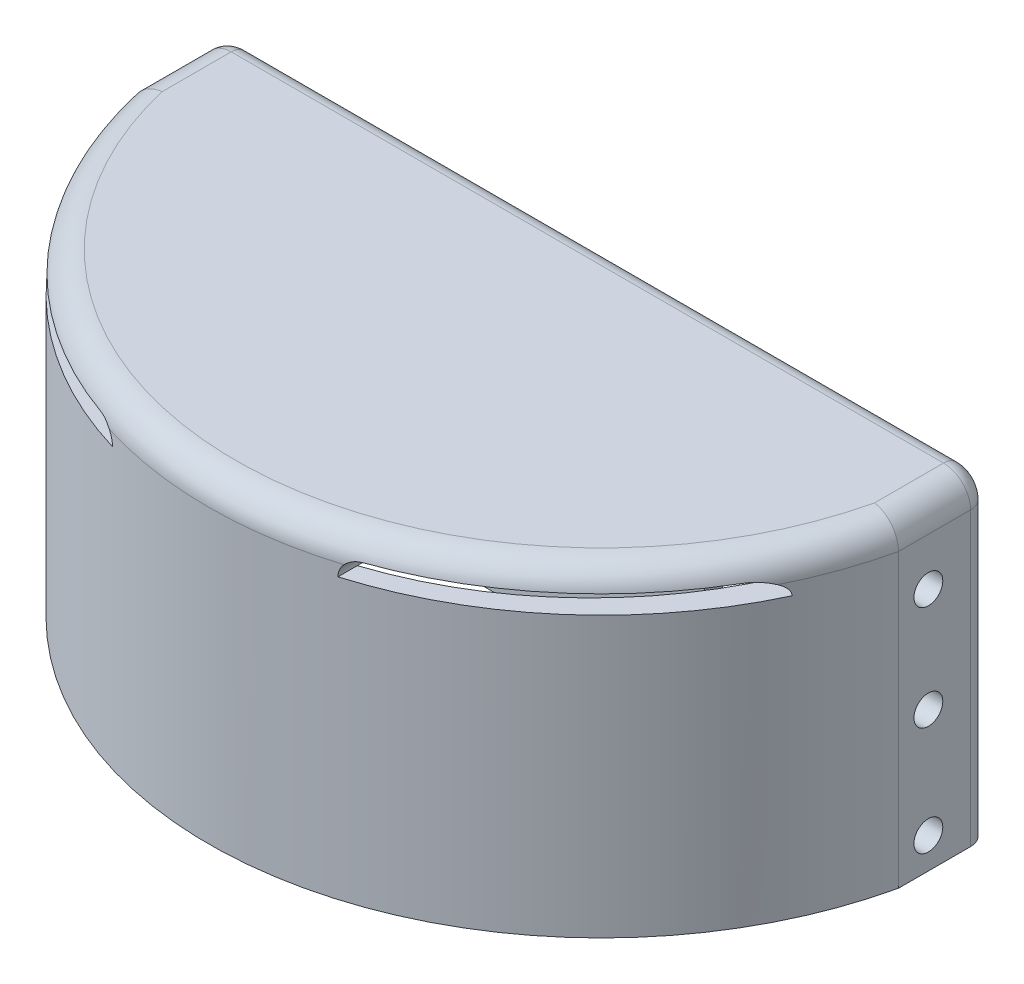
SolidWorks part; units mm, degrees
ref_plane "Ön Düzlem" through (0, 0, 0) normal (0, 0, 1) x (1, 0, 0)
ref_plane "Üst Düzlem" through (0, 0, 0) normal (0, 1, 0) x (1, 0, 0)
ref_plane "Sağ Düzlem" through (0, 0, 0) normal (1, 0, 0) x (0, 0, -1)
sketch "Çizim1" plane through (0, 0, 0) normal (0, 0, 1) x (1, 0, 0)
  line L1 (-11.5, 17.5) -> (11.5, 17.5)
  line L2 (-13.5, 15.5) -> (-13.5, -15.5)
  line L3 (-11.5, -17.5) -> (11.5, -17.5)
  line L4 (13.5, 15.5) -> (13.5, -15.5)
  circle A0 centre (-10, 14) radius 2.5
  circle A1 centre (-10, -14) radius 2.5
  circle A2 centre (10, 14) radius 2.5
  circle A3 centre (10, -14) radius 2.5
  arc A4 (11.5, -17.5) -> (13.5, -15.5) centre (11.5, -15.5) ccw
  arc A5 (-13.5, -15.5) -> (-11.5, -17.5) centre (-11.5, -15.5) ccw
  arc A6 (-11.5, 17.5) -> (-13.5, 15.5) centre (-11.5, 15.5) ccw
  arc A7 (11.5, 17.5) -> (13.5, 15.5) centre (11.5, 15.5) cw
  point P0 (0, 0)
  point P16 (13.5, -17.5)
  point P21 (-13.5, 17.5)
  point P24 (13.5, 17.5)
  dimension "D3" = 5
  dimension "D4" = 5
  dimension "D5" = 5
  dimension "D6" = 5
  dimension "D7" = 3.5
  dimension "D8" = 3.5
  dimension "D9" = 3.5
  dimension "D10" = 3.5
  dimension "D11" = 3.5
  dimension "D12" = 3.5
  dimension "D13" = 3.5
  dimension "D14" = 3.5
  dimension "D15" = 2
  dimension "D1" = 27
  dimension "D2" = 35
extrude "Yükseklik-Ekstrüzyon1" add sketch "Çizim1" along normal blind 2
sketch "Çizim2" plane through (0, 0, 0) normal (0, 0, -1) x (-1, 0, 0)
  line L0 (13.5, 15.5) -> (38.5, 15.5)
  line L1 (38.5, 15.5) -> (38.5, -15.5)
  line L2 (38.5, -15.5) -> (13.5, -15.5)
  line L3 (13.5, -15.5) -> (13.5, 15.5)
  dimension "D1" = 25
extrude "Yükseklik-Ekstrüzyon2" add sketch "Çizim2" against normal blind 2
sketch "Çizim3" plane through (0, 0, 0) normal (0, 0, -1) x (-1, 0, 0)
  line L0 (26, 15.5) -> (26, 12.3298)
  line L1 (38.5, 15.5) -> (13.5, 15.5) construction
  line L2 (26, 12.3298) -> (26.8882, 12.3298)
  line L3 (26.8882, 12.3298) -> (26.8882, 15.5)
  line L4 (26.8882, 15.5) -> (26, 15.5)
extrude "Kes-Ekstrüzyon1" cut sketch "Çizim3" against normal blind 2
mirror "Aynalama4" about plane through (-26, 15.5, 2) normal (1, 0, 0) of "Yükseklik-Ekstrüzyon1"
sketch "Çizim6" plane through (0, 0, 0) normal (0, 0, -1) x (-1, 0, 0)
  line L0 (-13.5, -15.5) -> (-13.5, 15.5) construction
  line L1 (-13.5, 15.5) -> (-16.5, 15.5)
  line L2 (-13.5, 15.5) -> (-13.5, -15.5)
  line L3 (-13.5, -15.5) -> (-16.5, -15.5)
  line L4 (-16.5, 15.5) -> (-16.5, -15.5)
  line L6 (65.5, 15.5) -> (68.5, 15.5)
  line L7 (65.5, 15.5) -> (65.5, -15.5)
  line L8 (65.5, -15.5) -> (68.5, -15.5)
  line L9 (68.5, 15.5) -> (68.5, -15.5)
  arc A0 (-11.5, 17.5) -> (-13.5, 15.5) centre (-11.5, 15.5) ccw construction
  dimension "D1" = 3
  dimension "D2" = 3
extrude "Yükseklik-Ekstrüzyon3" add sketch "Çizim6" against normal blind 10
sketch "Çizim7" plane through (16.5, 0, 0) normal (1, 0, 0) x (0, 0, -1)
  circle A0 centre (-6.6819, 11.5752) radius 1.6
  circle A1 centre (-6.6819, 0) radius 1.6
  circle A2 centre (-6.6819, -12.0698) radius 1.6
  dimension "D1" = 3.2
  dimension "D2" = 3.2
  dimension "D3" = 3.2
extrude "Kes-Ekstrüzyon2" cut sketch "Çizim7" against normal blind 141
sketch "Çizim8" plane through (0, 0, 0) normal (0, 0, -1) x (-1, 0, 0)
  line L0 (26, 15.5) -> (13.5, 15.5) construction
  line L1 (24.5276, 15.5) -> (29.0801, 15.5)
  line L2 (24.5276, 15.5) -> (24.5276, 9.757)
  line L3 (24.5276, 9.757) -> (29.0801, 9.757)
  line L4 (29.0801, 15.5) -> (29.0801, 9.757)
extrude "Yükseklik-Ekstrüzyon4" add sketch "Çizim8" against normal blind 2
sketch "Çizim9" plane through (0, -15.5, 0) normal (0, -1, 0) x (1, 0, 0)
  line L0 (-13.5, 2) -> (-38.5, 2) construction
  line L1 (-68.5, 10) -> (-65.5, 10)
  line L2 (13.5, 10) -> (16.5, 10)
  arc A0 (-65.5, 10) -> (13.5, 10) centre (-26, 1.6211) cw
  arc A1 (-68.5, 10) -> (16.5, 10) centre (-26, 0.4375) cw
  point P7 (-26, 42)
  point P11 (-26, 44)
  dimension "D1" = 40
  dimension "D2" = 42
extrude "Yükseklik-Ekstrüzyon5" add sketch "Çizim9" against normal up to surface (31 mm away) up to face at (14.7, 15.5, 4.4)
sketch "Çizim10" plane through (0, 0, 0) normal (0, 0, -1) x (-1, 0, 0)
  line L0 (-16.5, 15.5) -> (-16.5, 19.8453)
  line L1 (-16.5, 19.8453) -> (68.5, 19.8453)
  line L2 (68.5, 19.8453) -> (68.5, 15.5)
  line L12 (38.5, 15.5) -> (13.5, 15.5)
  line L13 (11.5, 17.5) -> (-11.5, 17.5)
  line L14 (-13.5, 15.5) -> (-16.5, 15.5)
  line L15 (-16.5, 15.5) -> (-16.5, -15.5)
  line L16 (-16.5, -15.5) -> (-13.5, -15.5)
  line L17 (-11.5, -17.5) -> (11.5, -17.5)
  line L18 (13.5, -15.5) -> (38.5, -15.5)
  line L19 (40.5, -17.5) -> (63.5, -17.5)
  line L20 (65.5, -15.5) -> (68.5, -15.5)
  line L21 (68.5, -15.5) -> (68.5, 15.5)
  line L22 (68.5, 15.5) -> (65.5, 15.5)
  line L23 (63.5, 17.5) -> (40.5, 17.5)
  line L24 (38.5, 15.5) -> (13.5, 15.5)
  line L25 (11.5, 17.5) -> (-11.5, 17.5)
  line L26 (-13.5, 15.5) -> (-16.5, 15.5)
  line L27 (-16.5, 15.5) -> (-16.5, -15.5)
  line L28 (-16.5, -15.5) -> (-13.5, -15.5)
  line L29 (-11.5, -17.5) -> (11.5, -17.5)
  line L30 (13.5, -15.5) -> (38.5, -15.5)
  line L31 (40.5, -17.5) -> (63.5, -17.5)
  line L32 (65.5, -15.5) -> (68.5, -15.5)
  line L33 (68.5, -15.5) -> (68.5, 15.5)
  line L34 (68.5, 15.5) -> (65.5, 15.5)
  line L35 (63.5, 17.5) -> (40.5, 17.5)
  arc A8 (13.5, 15.5) -> (11.5, 17.5) centre (11.5, 15.5) ccw
  arc A9 (-11.5, 17.5) -> (-13.5, 15.5) centre (-11.5, 15.5) ccw
  arc A10 (-13.5, -15.5) -> (-11.5, -17.5) centre (-11.5, -15.5) ccw
  arc A11 (11.5, -17.5) -> (13.5, -15.5) centre (11.5, -15.5) ccw
  arc A12 (38.5, -15.5) -> (40.5, -17.5) centre (40.5, -15.5) ccw
  arc A13 (63.5, -17.5) -> (65.5, -15.5) centre (63.5, -15.5) ccw
  arc A14 (65.5, 15.5) -> (63.5, 17.5) centre (63.5, 15.5) ccw
  arc A15 (40.5, 17.5) -> (38.5, 15.5) centre (40.5, 15.5) ccw
  arc A16 (13.5, 15.5) -> (11.5, 17.5) centre (11.5, 15.5) ccw
  arc A17 (-11.5, 17.5) -> (-13.5, 15.5) centre (-11.5, 15.5) ccw
  arc A18 (-13.5, -15.5) -> (-11.5, -17.5) centre (-11.5, -15.5) ccw
  arc A19 (11.5, -17.5) -> (13.5, -15.5) centre (11.5, -15.5) ccw
  arc A20 (38.5, -15.5) -> (40.5, -17.5) centre (40.5, -15.5) ccw
  arc A21 (63.5, -17.5) -> (65.5, -15.5) centre (63.5, -15.5) ccw
  arc A22 (65.5, 15.5) -> (63.5, 17.5) centre (63.5, 15.5) ccw
  arc A23 (40.5, 17.5) -> (38.5, 15.5) centre (40.5, 15.5) ccw
  line M21 (38.5, 15.5) -> (13.5, 15.5)
  arc M22 (13.5, 15.5) -> (11.5, 17.5) centre (11.5, 15.5) ccw
  line M23 (11.5, 17.5) -> (-11.5, 17.5)
  arc M24 (-11.5, 17.5) -> (-13.5, 15.5) centre (-11.5, 15.5) ccw
  line M25 (-13.5, 15.5) -> (-16.5, 15.5)
  line M37 (68.5, 15.5) -> (65.5, 15.5)
  arc M38 (65.5, 15.5) -> (63.5, 17.5) centre (63.5, 15.5) ccw
  line M39 (63.5, 17.5) -> (40.5, 17.5)
  arc M40 (40.5, 17.5) -> (38.5, 15.5) centre (40.5, 15.5) ccw
  dimension "D1" = 0
extrude "Yükseklik-Ekstrüzyon6" add sketch "Çizim10" against normal up to surface (10 mm away) contours L2 L1 L0 M25 M24 M23 M22 M21 M40 M39 M38 M37
fillet "Radyus1" radius 3 3 edges at (16.5, 19.8453, 5) (-68.5, 19.8453, 5) (-26, 19.8453, 0)
fillet "Radyus2" radius 2 5 edges at (16.5, 0.6726, 0) (15.6213, 18.9666, 0) (-68.5, 0.6726, 0) (-67.6213, 18.9666, 0) (-26, 19.8453, 0)
sketch "Çizim11" plane through (0, 0, 0) normal (0, 0, -1) x (-1, 0, 0)
  line L0 (66.5, -15.5) -> (66.5, 16.8453) construction
  line L1 (39, 11) -> (64, 11)
  line L2 (39, 11) -> (39, -9)
  line L3 (39, -9) -> (64, -9)
  line L4 (64, 11) -> (64, -9)
  line L5 (-12, 11) -> (13, 11)
  line L6 (-12, 11) -> (-12, -9)
  line L7 (-12, -9) -> (13, -9)
  line L8 (13, 11) -> (13, -9)
  line L9 (-14.5, 16.8453) -> (-14.5, -15.5) construction
  circle A0 centre (62, -14) radius 2.5 construction
  circle A1 centre (10, -14) radius 2.5 construction
  dimension "D1" = 25
  dimension "D2" = 20
  dimension "D3" = 5
  dimension "D4" = 5
  dimension "D5" = 25
  dimension "D6" = 2.5
  dimension "D7" = 2.5
  dimension "D8" = 20
extrude "Kes-Ekstrüzyon3" cut sketch "Çizim11" against normal blind 10
sketch "Çizim12" plane through (0, 0, 0) normal (0, 0, -1) x (-1, 0, 0)
  line L0 (11.5, -17.5) -> (40.5, -17.5)
  line L9 (-14.5, 16.8453) -> (-14.5, -15.5)
  line L10 (-14.5, -15.5) -> (-13.5, -15.5)
  line L11 (-11.5, -17.5) -> (11.5, -17.5)
  line L12 (13.5, -15.5) -> (38.5, -15.5)
  line L13 (40.5, -17.5) -> (63.5, -17.5)
  line L14 (65.5, -15.5) -> (66.5, -15.5)
  line L15 (66.5, -15.5) -> (66.5, 16.8453)
  line L16 (65.5, 17.8453) -> (-13.5, 17.8453)
  line L17 (-14.5, 16.8453) -> (-14.5, -15.5)
  line L18 (-14.5, -15.5) -> (-13.5, -15.5)
  line L19 (-11.5, -17.5) -> (11.5, -17.5)
  line L20 (13.5, -15.5) -> (38.5, -15.5)
  line L21 (40.5, -17.5) -> (63.5, -17.5)
  line L22 (65.5, -15.5) -> (66.5, -15.5)
  line L23 (66.5, -15.5) -> (66.5, 16.8453)
  line L24 (65.5, 17.8453) -> (-13.5, 17.8453)
  arc A6 (-13.5, 17.8453) -> (-14.5, 16.8453) centre (-13.5, 16.8453) ccw
  arc A7 (-13.5, -15.5) -> (-11.5, -17.5) centre (-11.5, -15.5) ccw
  arc A8 (11.5, -17.5) -> (13.5, -15.5) centre (11.5, -15.5) ccw
  arc A9 (38.5, -15.5) -> (40.5, -17.5) centre (40.5, -15.5) ccw
  arc A10 (63.5, -17.5) -> (65.5, -15.5) centre (63.5, -15.5) ccw
  arc A11 (66.5, 16.8453) -> (65.5, 17.8453) centre (65.5, 16.8453) ccw
  arc A12 (-13.5, 17.8453) -> (-14.5, 16.8453) centre (-13.5, 16.8453) ccw
  arc A13 (-13.5, -15.5) -> (-11.5, -17.5) centre (-11.5, -15.5) ccw
  arc A14 (11.5, -17.5) -> (13.5, -15.5) centre (11.5, -15.5) ccw
  arc A15 (38.5, -15.5) -> (40.5, -17.5) centre (40.5, -15.5) ccw
  arc A16 (63.5, -17.5) -> (65.5, -15.5) centre (63.5, -15.5) ccw
  arc A17 (66.5, 16.8453) -> (65.5, 17.8453) centre (65.5, 16.8453) ccw
  arc M28 (11.5, -17.5) -> (13.5, -15.5) centre (11.5, -15.5) ccw
  line M29 (13.5, -15.5) -> (38.5, -15.5)
  arc M30 (38.5, -15.5) -> (40.5, -17.5) centre (40.5, -15.5) ccw
  dimension "D1" = 0
extrude "Yükseklik-Ekstrüzyon7" add sketch "Çizim12" against normal up to surface (2 mm away) contours L0 M28 M30 M29 up to face at (-0.5, 1, 2)
